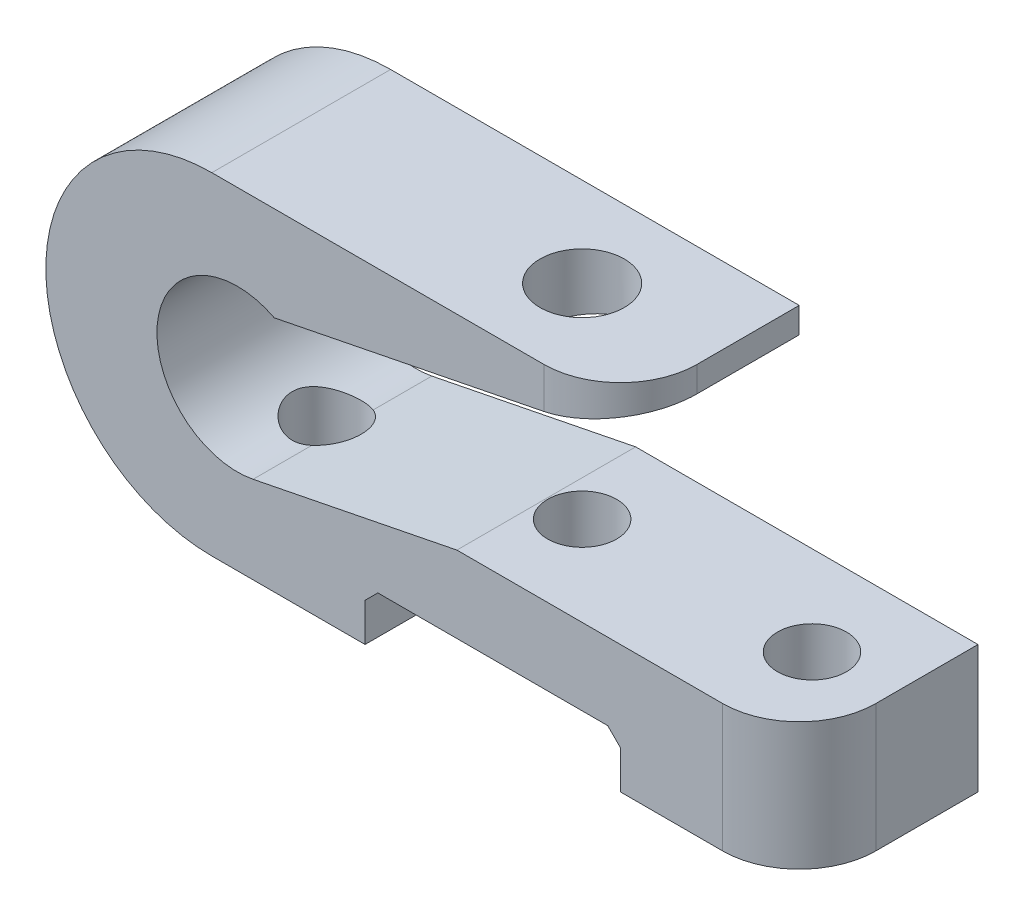
SolidWorks part; units mm, degrees
ref_plane "Front Plane" through (0, 0, 0) normal (0, 0, 1) x (1, 0, 0)
ref_plane "Top Plane" through (0, 0, 0) normal (0, 1, 0) x (1, 0, 0)
ref_plane "Right Plane" through (0, 0, 0) normal (1, 0, 0) x (0, 0, -1)
sketch "Sketch1" plane through (0, 0, 0) normal (0, 0, 1) x (1, 0, 0)
  line L0 (1.4431, 2.8) -> (15, 5.5)
  line L1 (15, 5.5) -> (15, 6.5)
  line L2 (15, 6.5) -> (-1, 6.5)
  line L4 (22, -1.5) -> (22, -6.5)
  line L5 (22, -6.5) -> (15, -6.5)
  line L6 (5, -6.5) -> (5, -4.5)
  line L7 (5, -4.5) -> (15, -4.5)
  line L8 (15, -4.5) -> (15, -6.5)
  line L9 (5, -6.5) -> (-1, -6.5)
  line L10 (0, 0) -> (-8.8114, 0) construction
  line L12 (8.5954, -1.5) -> (22, -1.5)
  line L15 (8.5954, -1.5) -> (0.6153, -3.0893)
  arc A0 (1.4431, 2.8) -> (0.6153, -3.0893) centre (0, 0) ccw
  arc A1 (-1, 6.5) -> (-1, -6.5) centre (-1, 0) ccw
  dimension "D1" = 3.15
  dimension "D2" = 13
  dimension "D3" = 1
  dimension "D4" = 2
  dimension "D5" = 22
  dimension "D6" = 5
  dimension "D7" = 10
  dimension "D8" = 1
  dimension "D9" = 5
  dimension "D10" = 2.8
extrude "Boss-Extrude1" add sketch "Sketch1" along normal blind 7
sketch "Sketch2" plane through (0, -6.5, 0) normal (0, -1, 0) x (1, 0, 0)
  line L0 (-9.2323, 3.5) -> (25.4054, 3.5) construction
  line L1 (0, 0) -> (0, 9.4448) construction
  line L2 (5, 7) -> (5, 0) construction
  circle A0 centre (0, 3.5) radius 1.35
  circle A1 centre (10, 3.5) radius 1.35
  circle A2 centre (19, 3.5) radius 1.35
  dimension "D2" = 2.7
  dimension "D1" = 19
  dimension "D3" = 5
  dimension "D4" = 3.5
extrude "Cut-Extrude1" cut sketch "Sketch2" against normal up to next
sketch "Sketch3" plane through (0, 6.5, 0) normal (0, 1, 0) x (1, 0, 0)
  circle A0 centre (10, -3.5) radius 1.65
  circle A1 centre (10, -3.5) radius 1.35 construction
  dimension "D1" = 3.3
extrude "Cut-Extrude2" cut sketch "Sketch3" against normal up to next
fillet "Fillet1" radius 3 2 edges at (15, 6, 7) (22, -4, 7)
chamfer "Chamfer2" distance 0.5 angle 45 2 edges at (15, -4.5, 3.5) (5, -4.5, 3.5)
